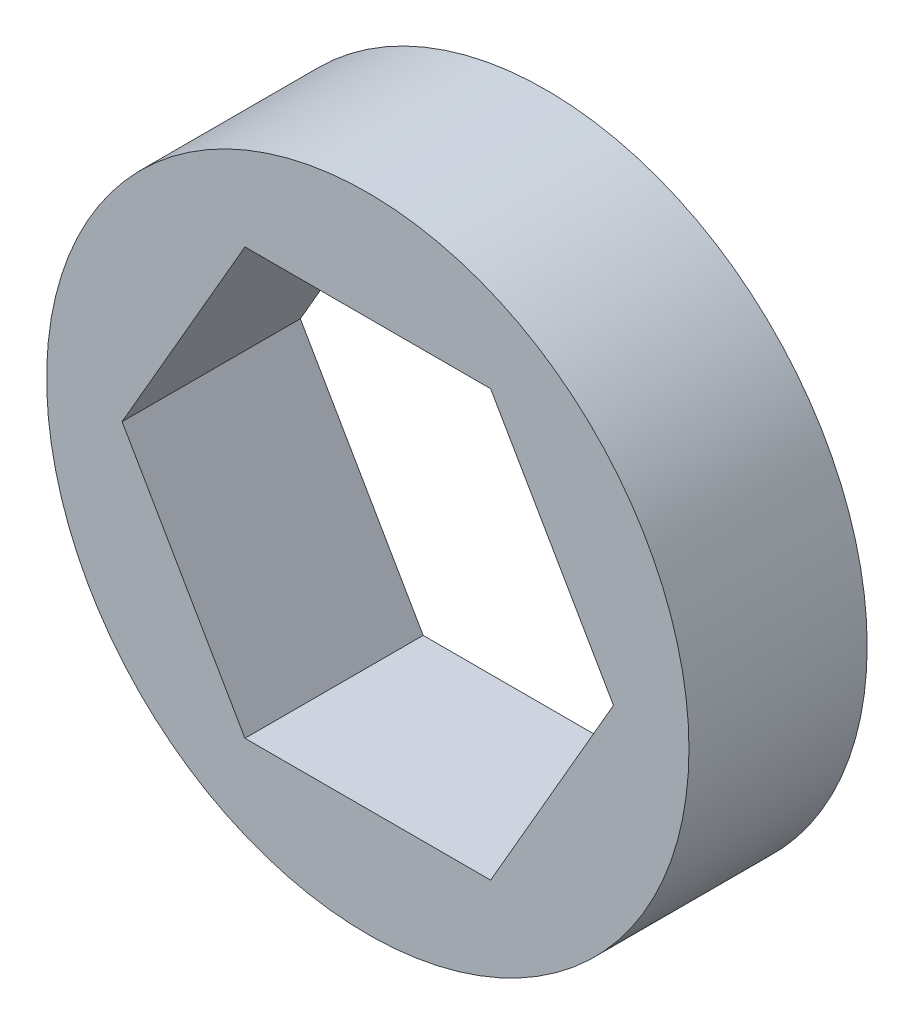
SolidWorks part; units mm, degrees
material "Nylon 101"
ref_plane "Front Plane" through (0, 0, 0) normal (0, 0, 1) x (1, 0, 0)
ref_plane "Top Plane" through (0, 0, 0) normal (0, 1, 0) x (1, 0, 0)
ref_plane "Right Plane" through (0, 0, 0) normal (1, 0, 0) x (0, 0, -1)
sketch "Sketch1" plane through (0, 0, 0) normal (0, 0, 1) x (1, 0, 0)
  line L1 (3.8861, 6.731) -> (-3.8861, 6.731)
  line L2 (-3.8861, 6.731) -> (-7.7723, 0)
  line L3 (-7.7723, 0) -> (-3.8861, -6.731)
  line L4 (-3.8861, -6.731) -> (3.8861, -6.731)
  line L5 (3.8861, -6.731) -> (7.7723, 0)
  line L6 (7.7723, 0) -> (3.8861, 6.731)
  circle A1 centre (0, 0) radius 10.16
  circle A2 centre (0, 0) radius 6.731 construction
  dimension "D1" = 20.32
  dimension ".5" = 13.462
extrude "Boss-Extrude1" add sketch "Sketch1" along normal blind 5.6375
sketch "Sketch2" plane through (0, 0, 0) normal (0, 0, -1) x (-1, 0, 0)
  line L0 (-3.6079, 7.366) -> (3.4241, 7.366) construction
  line L1 (-3.8861, 6.731) -> (3.8861, 6.731) construction
  text T0 "0048" font "Century Gothic" height in points 6
  dimension "D1" = 0.635
extrude "Cut-Extrude1" cut sketch "Sketch2" against normal blind 0.4
